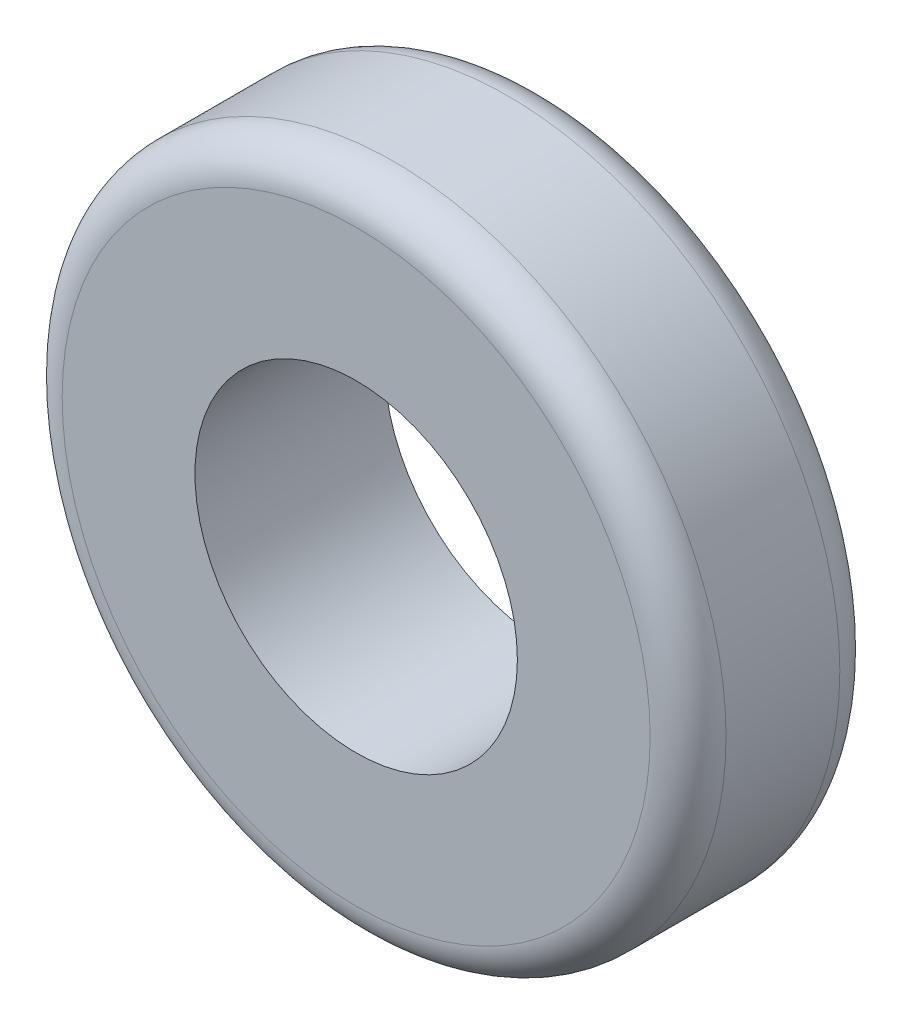
SolidWorks part; units mm, degrees
ref_plane "Front Plane" through (0, 0, 0) normal (0, 0, 1) x (1, 0, 0)
ref_plane "Top Plane" through (0, 0, 0) normal (0, 1, 0) x (1, 0, 0)
ref_plane "Right Plane" through (0, 0, 0) normal (1, 0, 0) x (0, 0, -1)
sketch "Sketch1" plane through (0, 0, 0) normal (0, 0, 1) x (1, 0, 0)
  circle A0 centre (0, 0) radius 17.5
  circle A1 centre (0, 0) radius 8.5
  dimension "D1" = 17
  dimension "D2" = 35
extrude "Boss-Extrude1" add sketch "Sketch1" along normal blind 10
fillet "Fillet1" radius 2 2 edges at (17.5, 0, 0) (17.5, 0, 10)
